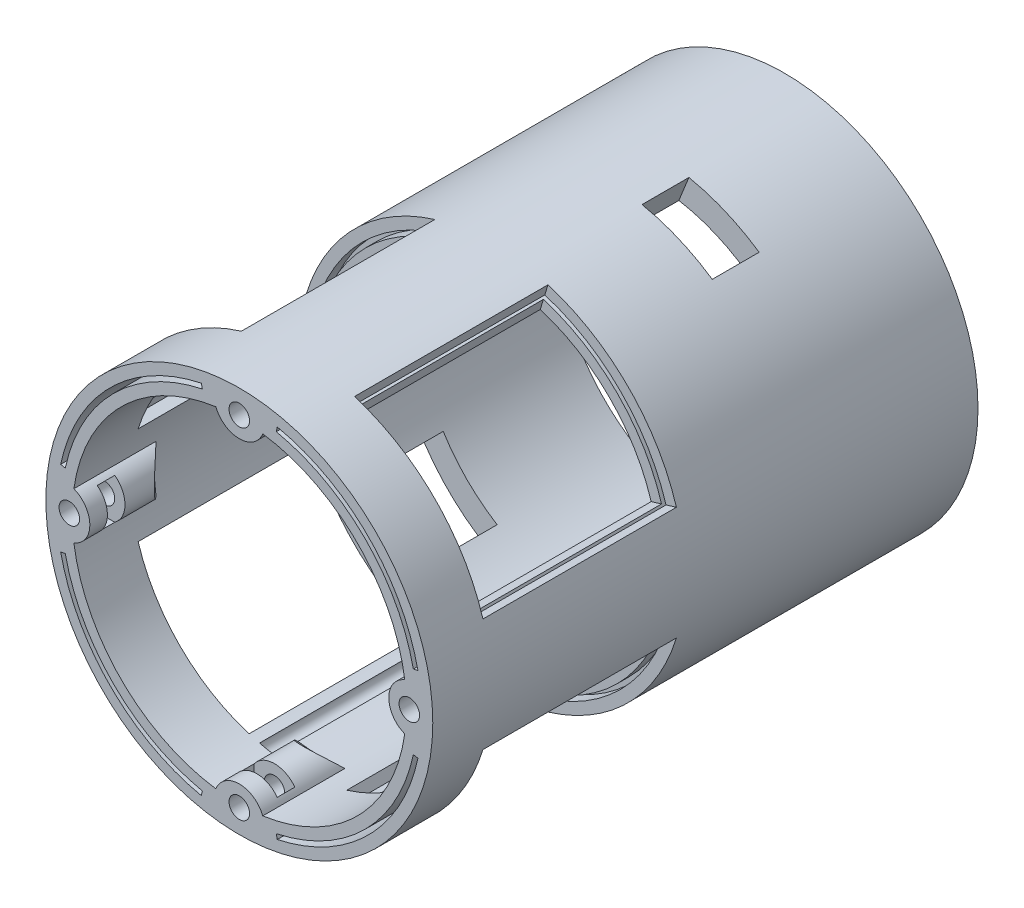
SolidWorks part; units mm, degrees
material "PEI"
ref_plane "Alzado" through (0, 0, 0) normal (0, 0, 1) x (1, 0, 0)
ref_plane "Planta" through (0, 0, 0) normal (0, 1, 0) x (1, 0, 0)
ref_plane "Vista lateral" through (0, 0, 0) normal (1, 0, 0) x (0, 0, -1)
sketch "Croquis1" plane through (0, 0, 0) normal (0, 0, 1) x (1, 0, 0)
  circle A0 centre (0, 0) radius 33
  circle A1 centre (0, 0) radius 28.5
  dimension "D1" = 66
  dimension "D2" = 4.5
extrude "Boss-Extrude1" add sketch "Croquis1" along normal blind 93
sketch "Croquis2" plane through (0, 0, 93) normal (0, 0, 1) x (1, 0, 0)
  line L0 (0, 0) -> (-6.4764, -30.4693) construction
  line L1 (0, 0) -> (-30.4693, -6.4764) construction
  line L2 (0, 0) -> (0, -30.5) construction
  line L3 (0, 0) -> (-30.5, 0) construction
  line L4 (-30.4693, -6.4764) -> (-29.6868, -6.3101)
  line L5 (-6.4764, -30.4693) -> (-6.3101, -29.6868)
  line L6 (-30.4693, 6.4764) -> (-29.6868, 6.3101)
  line L7 (-6.4764, 30.4693) -> (-6.3101, 29.6868)
  line L8 (6.4764, 30.4693) -> (6.3101, 29.6868)
  line L9 (30.4693, 6.4764) -> (29.6868, 6.3101)
  line L10 (30.4693, -6.4764) -> (29.6868, -6.3101)
  line L11 (6.4764, -30.4693) -> (6.3101, -29.6868)
  circle A0 centre (0, 0) radius 30.35 construction
  circle A1 centre (0, 0) radius 31.15 construction
  circle A2 centre (0, 0) radius 33 construction
  circle A3 centre (0, 0) radius 30.75 construction
  arc A4 (-6.4764, -30.4693) -> (-30.4693, -6.4764) centre (0, 0) cw
  arc A5 (-6.3101, -29.6868) -> (-29.6868, -6.3101) centre (0, 0) cw
  arc A6 (-30.4693, 6.4764) -> (-6.4764, 30.4693) centre (0, 0) cw
  arc A7 (-29.6868, 6.3101) -> (-6.3101, 29.6868) centre (0, 0) cw
  arc A8 (6.4764, 30.4693) -> (30.4693, 6.4764) centre (0, 0) cw
  arc A9 (6.3101, 29.6868) -> (29.6868, 6.3101) centre (0, 0) cw
  arc A10 (30.4693, -6.4764) -> (6.4764, -30.4693) centre (0, 0) cw
  arc A11 (29.6868, -6.3101) -> (6.3101, -29.6868) centre (0, 0) cw
  circle A12 centre (0, 0) radius 28.5 construction
  point P4 (-6.3933, -30.078)
  point P32 (0, 0)
  dimension "D3" = 12
  dimension "D4" = 12
  dimension "D1" = 0.8
  dimension "D2" = 4.5
  dimension "D6" = 2.25
  dimension "D5" = 4
extrude "Cortar-Extruir1" cut sketch "Croquis2" against normal blind 45
ref_axis "Eje1" through (0, 0, 93) along (0, 0, -1)
ref_plane "Plano2" through (0, 0, 0) normal (0.9563, -0.2924, 0) x (0, 0, -1)
sketch "Croquis4" plane through (0, 0, 0) normal (0.9563, -0.2924, 0) x (0, 0, -1)
  line L0 (-83, 33) -> (-83, 28.266)
  line L1 (0, 33) -> (-93, 33) construction
  line L2 (-83, 28.266) -> (-50, 28.266)
  line L4 (-50, 33) -> (-83, 33)
  line L5 (-97, 29) -> (-42, 29) construction
  line L6 (-93, 33) -> (-93, -33) construction
  line L14 (-50, 28.266) -> (-50, 33)
  dimension "D1" = 4.734
  dimension "D6" = 10
revolve "Cortar-Revolución2" cut sketch "Croquis4" angle 56 about axis through (0, 0, 93) along (0, 0, -1)
pattern_circular "MatrizC2" count 4 over 360 about axis through (0, 0, 93) along (0, 0, -1) of "Cortar-Revolución2"
sketch "Sketch8" plane through (0, 0, 0) normal (0, 0, -1) x (-1, 0, 0)
  arc A0 (-4, -28.2179) -> (4, -28.2179) centre (0, 0) ccw
  circle A1 centre (0, 0) radius 28.5 construction
  arc A2 (-4, -28.2179) -> (4, -28.2179) centre (0, -29.7959) cw
  arc A3 (-28.2179, 4) -> (-28.2179, -4) centre (0, 0) ccw
  arc A4 (-28.2179, 4) -> (-28.2179, -4) centre (-29.7959, 0) cw
  arc A5 (4, 28.2179) -> (-4, 28.2179) centre (0, 0) ccw
  arc A6 (4, 28.2179) -> (-4, 28.2179) centre (0, 29.7959) cw
  arc A7 (28.2179, -4) -> (28.2179, 4) centre (0, 0) ccw
  arc A8 (28.2179, -4) -> (28.2179, 4) centre (29.7959, 0) cw
  point P8 (0, -25.4959)
  point P20 (0, 0)
  dimension "D1" = 4.3
  dimension "D2" = 8
  dimension "D3" = 4
extrude "Boss-Extrude4" add sketch "Sketch8" against normal blind 11
sketch "Sketch9" plane through (0, 0, 0) normal (0, 0, -1) x (-1, 0, 0)
  circle A0 centre (0, -29) radius 1.75
  circle A1 centre (0, 0) radius 29 construction
  circle A2 centre (0, 0) radius 33 construction
  circle A3 centre (-29, 0) radius 1.75
  circle A4 centre (0, 29) radius 1.75
  circle A5 centre (29, 0) radius 1.75
  point P16 (0, 0)
  dimension "D1" = 4
  dimension "D2" = 3.5
  dimension "D3" = 4
extrude "Cut-Extrude3" cut sketch "Sketch9" against normal blind 10
ref_plane "Mid plane" through (0, 0, 46.5) normal (0, 0, 1) x (1, 0, 0)
mirror "Mirror1" about plane through (0, 0, 46.5) normal (0, 0, 1) of "Cut-Extrude3", "Boss-Extrude4"
ref_plane "Plano para USB y Switch" through (-23.3345, -23.3345, 0) normal (-0.7071, -0.7071, 0) x (0, 0, -1)
sketch "Sketch10" plane through (-23.3345, -23.3345, 0) normal (-0.7071, -0.7071, 0) x (0, 0, -1)
  line L0 (0, -33) -> (0, 33) construction
  line L1 (-10.5, 7.5) -> (-3.5, 7.5)
  line L2 (-10.5, 7.5) -> (-10.5, -7.5)
  line L3 (-10.5, -7.5) -> (-3.5, -7.5)
  line L4 (-3.5, 7.5) -> (-3.5, -7.5)
  line L5 (-10.5, 7.5) -> (-3.5, -7.5) construction
  line L6 (-10.5, -7.5) -> (-3.5, 7.5) construction
  line L8 (-42, 6.5) -> (-34, 6.5)
  line L9 (-42, 6.5) -> (-42, -6.5)
  line L10 (-42, -6.5) -> (-34, -6.5)
  line L11 (-34, 6.5) -> (-34, -6.5)
  line L12 (-42, 6.5) -> (-34, -6.5) construction
  line L13 (-42, -6.5) -> (-34, 6.5) construction
  point P0 (-7, 0)
  point P9 (-38, 0)
  dimension "D1" = 7
  dimension "D2" = 15
  dimension "D3" = 7
  dimension "D4" = 13
  dimension "D5" = 8
  dimension "D6" = 38
extrude "Corte USB y Switch" cut sketch "Sketch10" against normal blind 10
ref_plane "Plano USB PCB_C" through (12.362, 30.5971, 0) normal (0.3746, 0.9272, 0) x (0, 0, -1)
sketch "Sketch11" plane through (12.362, 30.5971, 0) normal (0.3746, 0.9272, 0) x (0, 0, -1)
  line L0 (0, -33) -> (0, 33) construction
  line L1 (-30.9, 6) -> (-22.9, 6)
  line L2 (-30.9, 6) -> (-30.9, -7)
  line L3 (-30.9, -7) -> (-22.9, -7)
  line L4 (-22.9, 6) -> (-22.9, -7)
  line L5 (-30.9, 6) -> (-22.9, -7) construction
  line L6 (-30.9, -7) -> (-22.9, 6) construction
  point P0 (-26.9, -0.5)
  dimension "D1" = 0.5
  dimension "D2" = 8
  dimension "D3" = 13
  dimension "D4" = 22.9
extrude "Cut-Extrude5" cut sketch "Sketch11" against normal blind 10
chamfer "Chamfer1" distance 3 angle 45 4 edges at (0, 28.5, 82) (-28.5, 0, 82) (28.5, 0, 82) (0, -28.5, 82)
ref_plane "Plano3" through (0, 0, 90) normal (0, 0, 1) x (1, 0, 0)
sketch "Croquis6" plane through (0, 0, 90) normal (0, 0, 1) x (1, 0, 0)
  line L0 (-3.4641, -29) -> (-3.4641, -27.2483)
  line L1 (-29, -3.4641) -> (-27.2483, -3.4641)
  line L2 (-29, -3.4641) -> (-26, -1.7321) construction
  line L3 (-26, -1.7321) -> (-26, 1.7321) construction
  line L4 (-3.4641, -29) -> (-1.7321, -32)
  line L5 (-1.7321, -32) -> (1.7321, -32)
  line L6 (1.7321, -32) -> (3.4641, -29)
  line L7 (3.4641, -29) -> (3.4641, -27.2483)
  line L8 (-26, 1.7321) -> (-29, 3.4641) construction
  line L9 (2.5981, -27.5) -> (1.7321, -26) [skipped]
  line L10 (-1.7321, -26) -> (-2.5981, -27.5) [skipped]
  line L11 (0, -26) -> (-1.7321, -26) [skipped]
  line L12 (-29, 3.4641) -> (-32, 1.7321)
  line L13 (-32, 1.7321) -> (-32, -1.7321)
  line L14 (-32, -1.7321) -> (-29, -3.4641)
  line L15 (-29, 3.4641) -> (-27.2483, 3.4641)
  line L16 (-3.4641, 29) -> (-3.4641, 27.2483)
  line L17 (1.7321, -32) -> (3.4641, -29)
  line L18 (3.4641, -29) -> (1.7321, -26) construction
  line L19 (1.7321, -26) -> (-1.7321, -26) construction
  line L20 (-1.7321, -26) -> (-3.4641, -29) construction
  line L21 (-3.4641, -29) -> (-1.7321, -32)
  line L22 (-1.7321, -32) -> (1.7321, -32)
  line L23 (3.4641, 29) -> (1.7321, 32)
  line L24 (1.7321, 32) -> (-1.7321, 32)
  line L25 (-1.7321, 32) -> (-3.4641, 29)
  line L26 (-3.4641, 29) -> (-1.7321, 26) construction
  line L27 (-1.7321, 26) -> (1.7321, 26) construction
  line L28 (1.7321, 26) -> (3.4641, 29) construction
  line L29 (3.4641, 29) -> (3.4641, 27.2483)
  line L30 (29, 3.4641) -> (27.2483, 3.4641)
  line L31 (29, 3.4641) -> (26, 1.7321) construction
  line L32 (26, 1.7321) -> (26, -1.7321) construction
  line L33 (26, -1.7321) -> (29, -3.4641) construction
  line L34 (29, -3.4641) -> (32, -1.7321)
  line L35 (32, -1.7321) -> (32, 1.7321)
  line L36 (32, 1.7321) -> (29, 3.4641)
  line L37 (29, -3.4641) -> (27.2483, -3.4641)
  circle A0 centre (0, -29) radius 3 construction
  arc A1 (4, -28.2179) -> (-4, -28.2179) centre (0, -29.7959) ccw construction
  arc A2 (3.4641, -27.2483) -> (-3.4641, -27.2483) centre (0, -29.7959) ccw
  circle A3 centre (-29, 0) radius 3 construction
  arc A4 (-28.2179, -4) -> (-28.2179, 4) centre (-29.7959, 0) ccw construction
  arc A5 (-27.2483, -3.4641) -> (-27.2483, 3.4641) centre (-29.7959, 0) ccw
  circle A6 centre (0, -29) radius 3 construction
  circle A7 centre (0, 29) radius 3 construction
  arc A8 (-4, 28.2179) -> (4, 28.2179) centre (0, 29.7959) ccw construction
  arc A9 (-3.4641, 27.2483) -> (3.4641, 27.2483) centre (0, 29.7959) ccw
  circle A10 centre (29, 0) radius 3 construction
  arc A11 (28.2179, 4) -> (28.2179, -4) centre (29.7959, 0) ccw construction
  arc A12 (27.2483, 3.4641) -> (27.2483, -3.4641) centre (29.7959, 0) ccw
  dimension "D1" = 6
  dimension "D2" = 6
  dimension "D3" = 6
  dimension "D4" = 6
extrude "Cortar-Extruir2" cut sketch "Croquis6" against normal blind 3 contours L7 A2 L0 L4 L5 L6 | L1 A5 L15 L12 L13 L14 | L30 A12 L37 L34 L35 L36 | L16 A9 L29 L23 L24 L25 region at (0, -28.7019, 90) region at (-28.7019, 0, 90) region at (0, 28.7019, 90) region at (28.7019, 0, 90)
mirror "Simetría1" about plane through (0, 0, 46.5) normal (0, 0, 1) of "Cortar-Extruir2"
sketch "Croquis7" plane through (0, 0, 0) normal (0, 0, -1) x (-1, 0, 0)
  circle A0 centre (5.2826, -28.0061) radius 1.3
  arc A1 (4, -28.2179) -> (28.2179, -4) centre (0, 0) ccw construction
  dimension "D1" = 2.6
extrude "Cortar-Extruir3" cut sketch "Croquis7" against normal up to surface (83 mm away) up to face at (-19.5889, -19.5889, 83)
equation "\"D6@Croquis2\"=\"D2@Croquis2\"/2"
